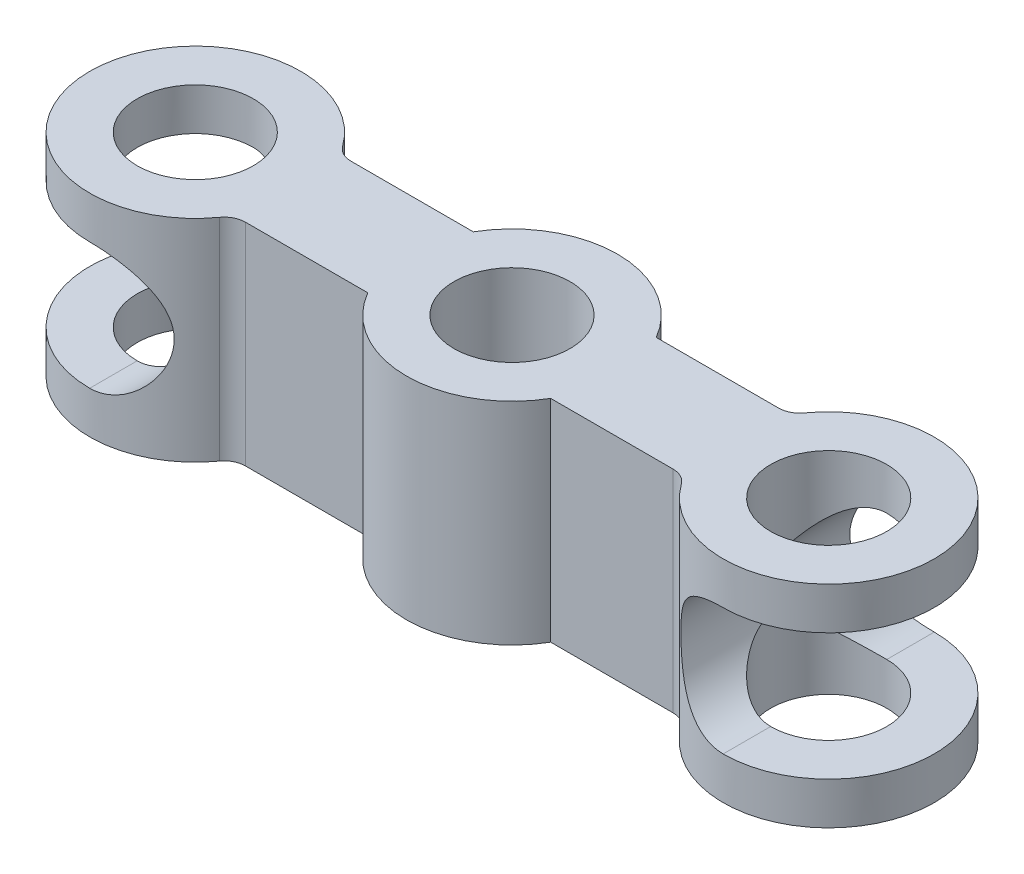
SolidWorks part; units mm, degrees
ref_plane "Front Plane" through (0, 0, 0) normal (0, 0, 1) x (1, 0, 0)
ref_plane "Top Plane" through (0, 0, 0) normal (0, 1, 0) x (1, 0, 0)
ref_plane "Right Plane" through (0, 0, 0) normal (1, 0, 0) x (0, 0, -1)
sketch "Sketch1" plane through (0, 0, 0) normal (0, 1, 0) x (1, 0, 0)
  line L1 (0, 2.5) -> (15, 2.5)
  line L2 (0, 2.5) -> (0, -2.5)
  line L3 (0, -2.5) -> (15, -2.5)
  line L4 (15, 2.5) -> (15, -2.5)
  dimension "D1" = 5
  dimension "D2" = 15
extrude "Boss-Extrude1" add sketch "Sketch1" along normal blind 10
sketch "Sketch2" plane through (0, 0, 0) normal (0, 1, 0) x (1, 0, 0)
  circle A0 centre (0, 0) radius 5
  dimension "D1" = 10
sketch "Sketch3" plane through (0, 0, 0) normal (0, 1, 0) x (1, 0, 0)
  circle A0 centre (0, 0) radius 2.75
  dimension "D1" = 5.5
extrude "Boss-Extrude2" add sketch "Sketch2" along normal up to surface (10 mm away) up to face at (7.5, 10, 0)
extrude "Cut-Extrude1" cut sketch "Sketch3" along normal up to next
sketch "Sketch4" plane through (0, 0, 0) normal (0, 0, 1) x (1, 0, 0)
  line L0 (0, 0) -> (0, 10) construction
  line L1 (2.75, 10) -> (-2.75, 10) construction
  line L2 (0, 8) -> (-5, 8)
  line L3 (-5, 10) -> (-5, 0) construction
  line L4 (0, 2) -> (-5, 2)
  line L5 (-5, 8) -> (-5, 2)
  arc A0 (0, 2) -> (0, 8) centre (0, 5) ccw
  dimension "D1" = 6
extrude "Cut-Extrude2" cut sketch "Sketch4" against normal through all both and the other way through all
fillet "Fillet1" radius 1 2 edges at (4.3301, 5, -2.5) (4.3301, 5, 2.5)
mirror "Mirror1" about plane through (15, 10, -2.5) normal (-1, 0, 0) of "Fillet1", "Cut-Extrude2", "Boss-Extrude2", "Cut-Extrude1", "Boss-Extrude1"
sketch "Sketch6" plane through (0, 0, 0) normal (0, 1, 0) x (1, 0, 0)
  circle A0 centre (15, 0) radius 5
  dimension "D1" = 10
  dimension "D2" = 0
  dimension "D3" = 15
extrude "Boss-Extrude3" add sketch "Sketch6" along normal up to surface (10 mm away) up to face at (30, 10, 2.75)
sketch "Sketch7" plane through (0, 0, 0) normal (0, 1, 0) x (1, 0, 0)
  circle A0 centre (15, 0) radius 2.75
  arc A1 (19.3301, 2.5) -> (10.6699, 2.5) centre (15, 0) ccw construction
  dimension "D1" = 5.5
extrude "Cut-Extrude3" cut sketch "Sketch7" along normal up to surface (10 mm away) up to face at (30, 10, 2.75)
